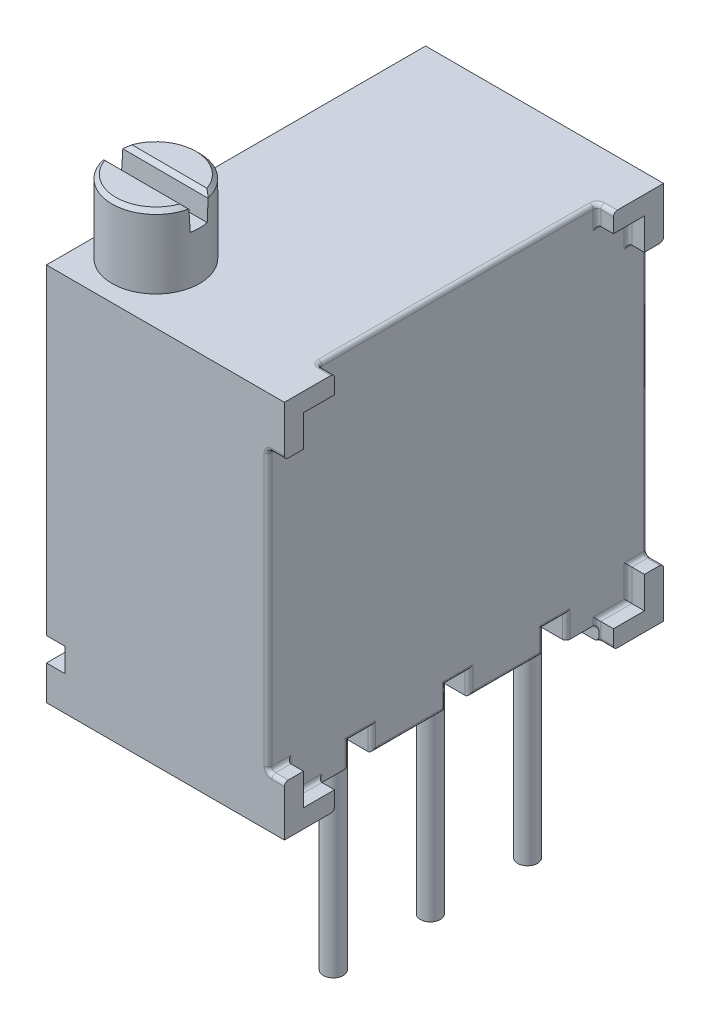
SolidWorks part; units mm, degrees
ref_plane "Front Plane" through (0, 0, 0) normal (0, 0, 1) x (1, 0, 0)
ref_plane "Top Plane" through (0, 0, 0) normal (0, 1, 0) x (1, 0, 0)
ref_plane "Right Plane" through (0, 0, 0) normal (1, 0, 0) x (0, 0, -1)
sketch "Sketch1" plane through (0, 0, 0) normal (0, 1, 0) x (1, 0, 0)
  line L0 (3.11, -4.955) -> (3.11, 4.955)
  line L1 (0, 0) -> (-3.11, 0) construction
  line L2 (0, 0) -> (0, 4.955) construction
  line L3 (3.11, 4.955) -> (-3.11, 4.955)
  line L4 (-3.11, -4.955) -> (-3.11, 4.955)
  line L5 (3.11, -4.955) -> (-3.11, -4.955)
  point P8 (3.11, 0)
  dimension "D1" = 3.11
  dimension "D2" = 4.955
  dimension "D3" = 6.22
  dimension "D4" = 9.91
extrude "Boss-Extrude1" add sketch "Sketch1" along normal blind 9.91
sketch "Sketch2" plane through (3.11, 0, 0) normal (1, 0, 0) x (0, 0, -1)
  line L0 (-4.955, 0) -> (4.955, 0) construction
  line L12 (-3.645, 9.91) -> (3.645, 9.91)
  line L13 (-3.645, 9.91) -> (-3.645, 9.4259)
  line L14 (4.955, 8.6) -> (4.955, 1.31)
  line L15 (0, 0) -> (0, 9.91) construction
  line L16 (-4.955, 9.91) -> (4.955, 9.91) construction
  line L17 (-4.955, 4.955) -> (0, 4.955) construction
  line L18 (-4.955, 9.91) -> (-4.955, 0) construction
  line L19 (4.955, 8.6) -> (4.455, 8.6)
  line L20 (-4.455, 9.4259) -> (-4.455, 8.6)
  line L21 (-3.645, 9.4259) -> (-4.455, 9.4259)
  line L22 (3.645, 9.4259) -> (4.455, 9.4259)
  line L23 (4.455, 9.4259) -> (4.455, 8.6)
  line L24 (-4.955, 8.6) -> (-4.455, 8.6)
  line L25 (3.645, 0) -> (-3.645, 0)
  line L26 (3.645, 9.91) -> (3.645, 9.4259)
  line L27 (-4.955, 1.31) -> (-4.955, 8.6)
  line L29 (3.645, 0) -> (3.645, 0.4841)
  line L31 (-4.955, 1.31) -> (-4.455, 1.31)
  line L32 (4.455, 0.4841) -> (4.455, 1.31)
  line L33 (3.645, 0.4841) -> (4.455, 0.4841)
  line L34 (-3.645, 0.4841) -> (-4.455, 0.4841)
  line L35 (-4.455, 0.4841) -> (-4.455, 1.31)
  line L36 (4.955, 1.31) -> (4.455, 1.31)
  line L38 (-3.645, 0) -> (-3.645, 0.4841)
  dimension "D1" = 1.31
  dimension "D2" = 1.31
extrude "Cut-Extrude1" cut sketch "Sketch2" against normal blind 0.43
sketch "Sketch3" plane through (0, 0, 4.955) normal (0, 0, 1) x (1, 0, 0)
  line L0 (-3.11, 9.91) -> (-3.11, 0) construction
  line L1 (-3.11, 0.9) -> (-2.6202, 0.9)
  line L2 (-3.11, 0.9) -> (-3.11, 1.52)
  line L3 (-3.11, 1.52) -> (-2.6202, 1.52)
  line L4 (-2.6202, 0.9) -> (-2.6202, 1.52)
  line L5 (-3.11, 0) -> (3.11, 0) construction
  dimension "D1" = 0.9
  dimension "D2" = 0.62
extrude "Cut-Extrude2" cut sketch "Sketch3" against normal through all
sketch "Sketch4" plane through (-3.11, 0, 0) normal (-1, 0, 0) x (0, 0, 1)
  line L0 (-4.955, 0) -> (4.955, 0) construction
  line L1 (-3.635, 0) -> (3.635, 0)
  line L2 (-3.635, 0) -> (-3.635, 0.3836)
  line L3 (-3.635, 0.3836) -> (3.635, 0.3836)
  line L4 (0, 0) -> (0, 0.3836) construction
  line L5 (-4.955, 0.9) -> (-4.955, 0) construction
  line L6 (3.635, 0) -> (3.635, 0.3836)
  dimension "D1" = 1.32
extrude "Cut-Extrude3" cut sketch "Sketch4" against normal through all
sketch "Sketch5" plane through (0, 0.3836, 0) normal (0, -1, 0) x (1, 0, 0)
  line L0 (0, 0) -> (4.882, 0) construction
  line L1 (0, -2.54) -> (4.882, -2.54) construction
  line L2 (2.9568, -0.2978) -> (2.0061, -0.2978)
  line L3 (2.9568, 0.2978) -> (2.0061, 0.2978)
  line L4 (0, 2.54) -> (4.882, 2.54) construction
  line L5 (2.9568, 2.8378) -> (2.9568, 2.2422)
  line L6 (2.9568, 2.8378) -> (2.0061, 2.8378)
  line L7 (2.9568, 2.2422) -> (2.0061, 2.2422)
  line L8 (2.9568, 0.2978) -> (2.9568, -0.2978)
  line L9 (2.9568, -2.2422) -> (2.9568, -2.8378)
  line L10 (3.11, 4.955) -> (3.11, 3.645) construction
  line L11 (2.9568, -2.2422) -> (2.0061, -2.2422)
  line L12 (2.9568, -2.8378) -> (2.0061, -2.8378)
  arc A0 (2.0061, 2.8378) -> (2.0061, 2.2422) centre (1.97, 2.54) ccw
  arc A1 (2.0061, 0.2978) -> (2.0061, -0.2978) centre (1.97, 0) ccw
  arc A2 (2.0061, -2.2422) -> (2.0061, -2.8378) centre (1.97, -2.54) ccw
  point P5 (0, -2.99)
  point P6 (4.882, -2.99)
  point P7 (0, -2.09)
  point P8 (4.882, -2.09)
  point P9 (0, -2.84)
  point P10 (4.882, -2.84)
  point P11 (0, -2.24)
  point P12 (4.882, -2.24)
  point P30 (3.11, 4.3)
  dimension "D1" = 1.14
extrude "Cut-Extrude4" cut sketch "Sketch5" against normal blind 0.6
sketch "Sketch6" plane through (0, 0.9836, 0) normal (0, -1, 0) x (1, 0, 0)
  line L1 (3.11, -3.645) -> (3.11, -4.955) construction
  circle A0 centre (1.97, 0) radius 0.26
  circle A1 centre (1.97, 2.537) radius 0.26
  circle A2 centre (1.97, -2.54) radius 0.26
  dimension "D1" = 1.14
extrude "Boss-Extrude2" add sketch "Sketch6" along normal blind 5.7
sketch "Sketch7" plane through (0, 9.91, 0) normal (0, 1, 0) x (1, 0, 0)
  line L2 (-3.11, -3.375) -> (3.11, -3.375)
  line L3 (-3.11, -3.375) -> (3.11, -3.375) construction
  circle A0 centre (-1.83, -3.375) radius 1.145
  dimension "D3" = 3.8
  dimension "D1" = 1.58
extrude "Boss-Extrude3" add sketch "Sketch7" along normal blind 1.9
sketch "Sketch8" plane through (0, 11.81, 0) normal (0, 1, 0) x (1, 0, 0)
  line L0 (-1.83, -3.375) -> (-0.3703, -3.3792) construction
  line L1 (-3.2943, -3.6258) -> (-0.371, -3.6342)
  line L2 (-3.296, -3.1158) -> (-0.3695, -3.1242)
  line L3 (-1.8293, -3.12) -> (-0.3695, -3.1242) construction
  line L4 (-1.8307, -3.63) -> (-0.371, -3.6342) construction
  line L5 (-3.2943, -3.6258) -> (-3.296, -3.1158)
  line L6 (-0.3695, -3.1242) -> (-0.371, -3.6342)
  dimension "D1" = 0.255
  dimension "D2" = 0.255
extrude "Cut-Extrude5" cut sketch "Sketch8" against normal blind 0.64 draft 3
chamfer "Chamfer1" distance 0.1 angle 45 4 edges at (-1.8267, 11.81, 2.23) (-1.8293, 11.81, 3.12) (-1.8307, 11.81, 3.63) (-1.8333, 11.81, 4.52)
fillet "Fillet1" radius 0.1 2 edges at (-0.215, 0.3836, -3.635) (-0.215, 0.3836, 3.635)
fillet "Fillet2" radius 0.1 38 edges at (2.895, 0, 3.645) (2.895, 1.31, 4.955) (2.895, 8.6, 4.955) (2.895, 9.91, 3.645) (2.895, 9.91, -3.645) (2.895, 8.6, -4.955) (2.895, 1.31, -4.955) (2.895, 0, -3.645) (2.68, 0.2421, 3.645) (2.68, 0.4841, 4.05) (2.68, 0.8971, 4.455) (2.68, 1.31, 4.705) (2.68, 4.955, 4.955) (2.68, 8.6, 4.705) (2.68, 9.0129, 4.455) (2.68, 9.4259, 4.05) (2.68, 9.6679, 3.645) (2.68, 9.91, 0) (2.68, 9.6679, -3.645) (2.68, 9.4259, -4.05) (2.68, 9.0129, -4.455) (2.68, 8.6, -4.705) (2.68, 4.955, -4.955) (2.68, 1.31, -4.705) (2.68, 0.8971, -4.455) (2.68, 0.4841, -4.05) (2.68, 0.2421, -3.645) (2.68, 0.3836, -1.27) (2.68, 0.6836, -0.2978) (2.68, 0.9836, 0) (2.68, 0.6836, 0.2978) (2.68, 0.3836, 1.27) (2.68, 0.6836, 2.2422) (2.68, 0.9836, 2.54) (2.68, 0.6836, 2.8378) (2.68, 0.6836, -2.8378) (2.68, 0.9836, -2.54) (2.68, 0.6836, -2.2422)
sketch "Sketch9" plane through (-3.11, 0, 0) normal (-1, 0, 0) x (0, 0, 1)
  text T0 "1" font "Century Gothic" height 1
  text T1 "2" font "Century Gothic" height 1
  text T2 "3" font "Century Gothic" height 1
extrude "Cut-Extrude6" cut sketch "Sketch9" against normal blind 0.1
